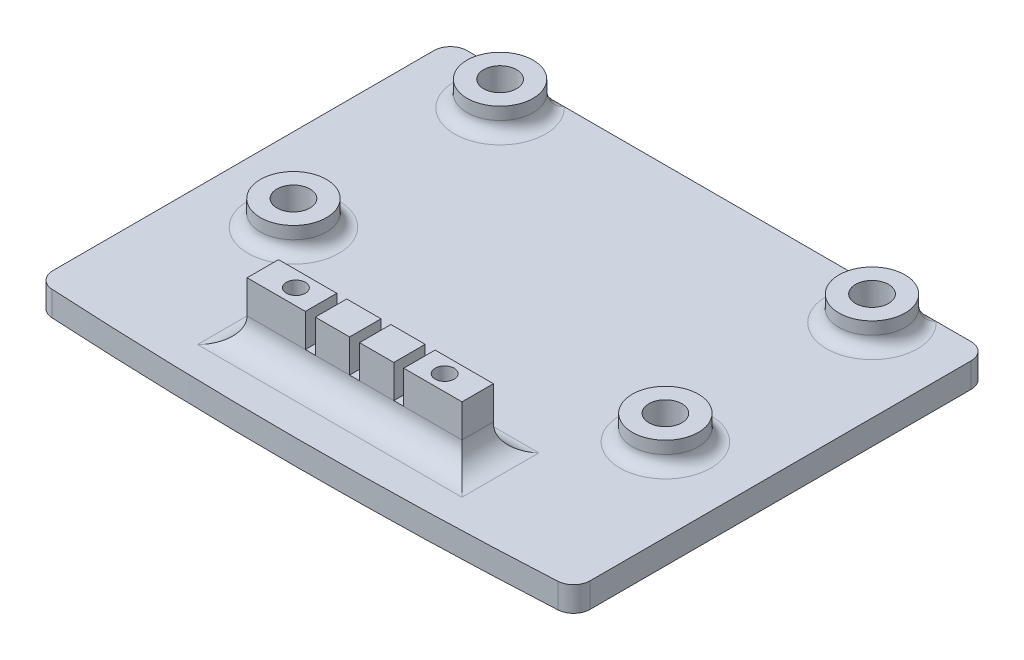
SolidWorks part; units mm, degrees
ref_plane "Ebene vorne" through (0, 0, 0) normal (0, 0, 1) x (1, 0, 0)
ref_plane "Ebene oben" through (0, 0, 0) normal (0, 1, 0) x (1, 0, 0)
ref_plane "Ebene rechts" through (0, 0, 0) normal (1, 0, 0) x (0, 0, -1)
sketch "Skizze1" plane through (0, 0, 0) normal (0, 1, 0) x (1, 0, 0)
  line L1 (-32.5, 0) -> (32.5, 0) construction
  line L2 (-32.5, 0) -> (-32.5, 50)
  line L3 (-32.5, 50) -> (32.5, 50)
  line L4 (32.5, 0) -> (32.5, 50)
  arc A0 (-32.5, 0) -> (32.5, 0) centre (0, 559.0561) ccw
  point P4 (0, 0)
  dimension "D3" = 560
  dimension "D1" = 65
  dimension "D2" = 50
extrude "Aufsatz-Linear austragen1" add sketch "Skizze1" along normal blind 3
fillet "Verrundung1" radius 2 4 edges at (-32.5, 1.5, -50) (32.5, 1.5, -50) (32.5, 1.5, 0) (-32.5, 1.5, 0)
sketch "Skizze10" plane through (0, 3, 0) normal (0, 1, 0) x (1, 0, 0)
  line L0 (30.5, 50) -> (-30.5, 50) construction
  line L1 (-22.5, 46) -> (22.5, 46) construction
  line L2 (-22.5, 46) -> (-22.5, 21) construction
  line L3 (-22.5, 21) -> (22.5, 21) construction
  line L4 (22.5, 46) -> (22.5, 21) construction
  circle A0 centre (-22.5, 46) radius 4
  circle A1 centre (-22.5, 21) radius 4
  circle A2 centre (22.5, 46) radius 4
  circle A3 centre (22.5, 21) radius 4
  point P2 (0, 21)
  dimension "D1" = 8
  dimension "D2" = 45
  dimension "D3" = 25
  dimension "D4" = 4
extrude "Aufsatz-Linear austragen4" add sketch "Skizze10" along normal blind 3
hole_wizard "Ø4.7 (4.75) Durchmesser Bohrung1" positions "Skizze2" profile "Skizze3" hole size "Ø4.7" standard "ANSI Metrisch" end condition through all
sketch "Skizze2" plane through (0, 0, 0) normal (0, 1, 0) x (1, 0, 0)
  line L1 (-22.5, 21) -> (22.5, 21)
  line L2 (-22.5, 21) -> (-22.5, 46)
  line L3 (-22.5, 46) -> (22.5, 46)
  line L4 (22.5, 21) -> (22.5, 46)
  line L5 (30.5, 50) -> (22.5, 50) construction
  point P0 (-22.5, 21)
  point P1 (22.5, 46)
  point P74 (-22.5, 46)
  point P75 (22.5, 21)
  point P77 (0, 21)
  dimension "D1" = 45
  dimension "D2" = 25
  dimension "D3" = 4
sketch "Skizze3" plane through (-22.5, 0, -21) normal (1, 0, 0) x (0, 0, -1)
  line L0 (0, 0) -> (0, 6)
  line L1 (0, 6) -> (2, 6)
  line L2 (2, 6) -> (2, 0)
  line L5 (2, 0) -> (0, 0)
  line L11 (0, -6.35) -> (0, 107.95) construction
  dimension "Bohrerdurchmesser" = 4
  dimension "Bohrungstiefe" = 6
sketch "Skizze9" plane through (0, 3, 0) normal (0, 1, 0) x (1, 0, 0)
  line L1 (-20, 19.4134) -> (20, 19.4134)
  line L2 (-20, 19.4134) -> (-20, -0.5866)
  line L3 (-20, -0.5866) -> (20, -0.5866) construction
  line L4 (20, 19.4134) -> (20, -0.5866)
  arc A0 (-30.6093, -0.1067) -> (30.6093, -0.1067) centre (0, 559.0561) ccw construction
  arc A1 (-20, -0.5866) -> (20, -0.5866) centre (0, 559.0561) ccw
  point P4 (0, 19.4134)
  dimension "D1" = 20
  dimension "D2" = 40
sketch "Skizze8" plane through (0, 0, 0) normal (1, 0, 0) x (0, 0, -1)
  line L0 (5.8933, 3) -> (5.8933, 10)
  line L1 (1.8903, 3) -> (48, 3) construction
  line L2 (5.8933, 10) -> (9.6933, 10)
  line L3 (9.6933, 10) -> (9.6933, 3)
  line L4 (9.6933, 3) -> (5.8933, 3)
  line L6 (19.4134, 3) -> (-0.5866, 3) construction
  dimension "D1" = 90
  dimension "D2" = 7
  dimension "D3" = 3.8
  dimension "D4" = 6
extrude "Aufsatz-Linear austragen3" add sketch "Skizze8" along normal mid plane 26
sketch "Skizze4" plane through (0, 3, 0) normal (0, 1, 0) x (1, 0, 0)
  line L1 (-13, 13.8) -> (13, 13.8)
  line L2 (-13, 13.8) -> (-13, 10)
  line L3 (-13, 10) -> (13, 10)
  line L4 (13, 13.8) -> (13, 10)
  point P4 (0, 10)
  dimension "D1" = 10
  dimension "D2" = 3.8
  dimension "D3" = 26
ref_plane "Ebene1" through (0, -2, 0) normal (0, 1, 0) x (1, 0, 0)
hole_wizard "Stirnsenkung für M3 Senkschraube (Kopf Button)4" positions "Skizze5" profile "Skizze6" counterbore size "M3" standard "ANSI Metrisch" end condition through all
sketch "Skizze5" plane through (0, -2, 1.9177) normal (0, -1, 0) x (-1, 0, 0)
  line L0 (9, 9.711) -> (-9, 9.711)
  line L2 (0, 7.811) -> (0, 11.611) construction
  point P0 (9, 9.711)
  point P2 (-9, 9.711)
  point P8 (0, 9.711)
  point P12 (0, 9.711)
  dimension "D1" = 18
sketch "Skizze6" plane through (-9, -2, -7.7933) normal (1, 0, 0) x (0, 0, -1)
  line L0 (0, 0) -> (0, 12)
  line L1 (0, 12) -> (1.15, 12)
  line L3 (1.15, 12) -> (1.15, 4)
  line L4 (1.15, 4) -> (3, 4)
  line L5 (3, 4) -> (3, 0)
  line L7 (3, 0) -> (0, 0)
  line L11 (0, -6.35) -> (0, 107.95) construction
  dimension "Bohrerdurchmesser" = 2.3
  dimension "Bohrungstiefe" = 12
  dimension "Senkdurchmesser2" = 6
  dimension "Senktiefe2" = 4
sketch "Skizze7" plane through (0, 10, 0) normal (0, 1, 0) x (1, 0, 0)
  line L6 (0.6, 9.6933) -> (0.6, 5.8933)
  line L11 (-5.95, 9.6933) -> (-4.75, 9.6933)
  line L12 (-5.95, 9.6933) -> (-5.95, 5.8933)
  line L13 (-5.95, 5.8933) -> (-4.75, 5.8933)
  line L14 (-4.75, 9.6933) -> (-4.75, 5.8933)
  line L15 (-0.6, 5.8933) -> (0.6, 5.8933)
  line L16 (-0.6, 9.6933) -> (-0.6, 5.8933)
  line L17 (-0.6, 9.6933) -> (0.6, 9.6933)
  line L18 (5.95, 9.6933) -> (5.95, 5.8933)
  line L19 (4.75, 5.8933) -> (5.95, 5.8933)
  line L20 (4.75, 9.6933) -> (4.75, 5.8933)
  line L21 (4.75, 9.6933) -> (5.95, 9.6933)
  line L22 (13, 5.8933) -> (-13, 5.8933) construction
  line L23 (13, 9.6933) -> (-13, 9.6933) construction
  point P0 (-5.35, 5.8933)
  dimension "D1" = 5.35
  dimension "D2" = 1.2
  dimension "D3" = 3
extrude "Schnitt-Linear austragen1" cut sketch "Skizze7" against normal blind 4
fillet "Verrundung2" radius 1.5 4 edges at (-22.5, 3, -42) (-22.5, 3, -17) (22.5, 3, -42) (22.5, 3, -17)
fillet "Verrundung5" radius 3 3 edges at (-13, 3, -7.7933) (13, 3, -7.7933) (0, 3, -5.8933)
fillet "Verrundung6" radius 2.5 1 edges at (0, 3, -9.6933)
